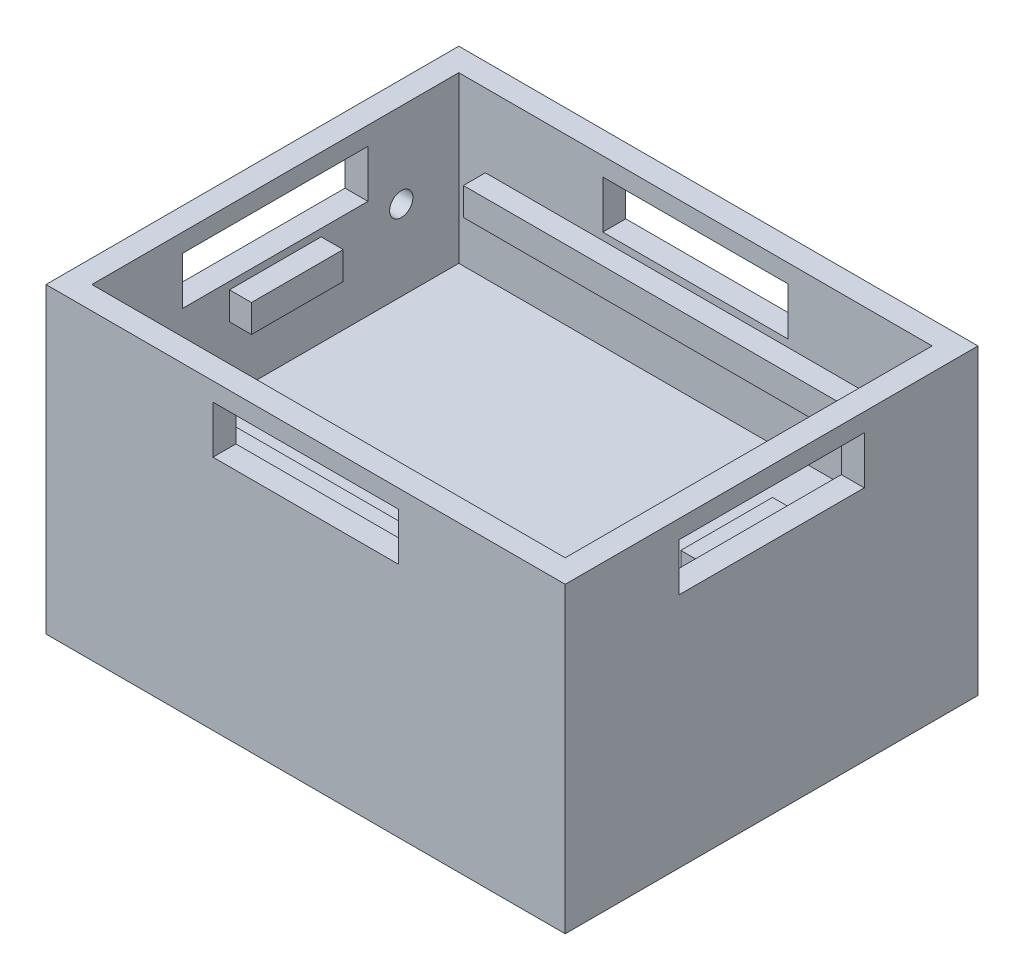
SolidWorks part; units mm, degrees
ref_plane "Front Plane" through (0, 0, 0) normal (0, 0, 1) x (1, 0, 0)
ref_plane "Top Plane" through (0, 0, 0) normal (0, 1, 0) x (1, 0, 0)
ref_plane "Right Plane" through (0, 0, 0) normal (1, 0, 0) x (0, 0, -1)
sketch "Sketch1" plane through (0, 0, 0) normal (0, 1, 0) x (1, 0, 0)
  line L0 (-2.5, 2.5) -> (-2.5, 202.5)
  line L5 (-15, -10) -> (268, -10)
  line L6 (-15, -10) -> (-15, 215)
  line L7 (-15, 215) -> (268, 215)
  line L8 (268, -10) -> (268, 215)
  line L9 (-2.5, 202.5) -> (255.5, 202.5)
  line L10 (255.5, 2.5) -> (255.5, 202.5)
  line L11 (-2.5, 2.5) -> (255.5, 2.5)
  dimension "D1" = 283
  dimension "D2" = 225
  dimension "D3" = 12.5
extrude "Walls" add sketch "Sketch1" along normal blind 90
sketch "Sketch3" plane through (0, 0, 0) normal (0, -1, 0) x (1, 0, 0)
  line L0 (268, -215) -> (-15, -215) construction
  line L1 (268, 10) -> (268, -215) construction
  line L2 (-15, 10) -> (268, 10) construction
  line L3 (-15, -215) -> (-15, 10) construction
  line L4 (268, -215) -> (-15, -215)
  line L5 (268, 10) -> (268, -215)
  line L6 (-15, 10) -> (268, 10)
  line L7 (-15, -215) -> (-15, 10)
extrude "Base" add sketch "Sketch3" along normal blind 12.5
ref_plane "Long_Support_Midplane" through (126.5, 0, 0) normal (1, 0, 0) x (0, 0, -1)
sketch "Sketch4" plane through (126.5, 0, 0) normal (1, 0, 0) x (0, 0, -1)
  line L0 (2.5, 0) -> (2.5, 90)
  line L1 (2.5, 50) -> (14.5, 50)
  line L2 (2.5, 50) -> (2.5, 34.9)
  line L3 (2.5, 34.9) -> (14.5, 34.9)
  line L4 (14.5, 50) -> (14.5, 34.9)
  line L5 (2.5, 0) -> (2.5, 90) construction
  line L6 (202.5, 50) -> (190.5, 50)
  line L7 (202.5, 50) -> (202.5, 34.9)
  line L8 (202.5, 34.9) -> (190.5, 34.9)
  line L9 (190.5, 50) -> (190.5, 34.9)
  line L14 (2.5, 0) -> (202.5, 0)
  line L15 (202.5, 0) -> (202.5, 90)
  line L16 (202.5, 90) -> (2.5, 90)
  line L17 (2.5, 90) -> (2.5, 0)
  line L18 (2.5, 0) -> (202.5, 0) construction
  line L19 (202.5, 0) -> (202.5, 90) construction
  line L20 (202.5, 90) -> (2.5, 90) construction
  line L21 (2.5, 90) -> (2.5, 0) construction
  dimension "D1" = 15.1
  dimension "D2" = 12
  dimension "D4" = 50
extrude "Long_Support" add sketch "Sketch4" along normal mid plane 229
ref_plane "Short_Support_Midplane" through (0, 0, -102.5) normal (0, 0, -1) x (-1, 0, 0)
sketch "Sketch5" plane through (0, 0, -102.5) normal (0, 0, -1) x (-1, 0, 0)
  line L1 (-255.5, 50) -> (-243.5, 50)
  line L2 (-255.5, 50) -> (-255.5, 34.9)
  line L3 (-255.5, 34.9) -> (-243.5, 34.9)
  line L4 (-243.5, 50) -> (-243.5, 34.9)
  line L5 (2.5, 50) -> (-9.5, 50)
  line L6 (2.5, 50) -> (2.5, 34.9)
  line L7 (2.5, 34.9) -> (-9.5, 34.9)
  line L8 (-9.5, 50) -> (-9.5, 34.9)
  line L12 (-255.5, 0) -> (2.5, 0)
  line L13 (2.5, 0) -> (2.5, 90)
  line L14 (2.5, 90) -> (-255.5, 90)
  line L15 (2.5, 0) -> (2.5, 90) construction
  line L16 (-255.5, 0) -> (2.5, 0) construction
  line L20 (-255.5, 90) -> (-255.5, 0)
  line L21 (-255.5, 90) -> (-255.5, 0) construction
  line L22 (2.5, 90) -> (-255.5, 90) construction
  dimension "D4" = 50
  dimension "D2" = 15.1
extrude "Short_Support" add sketch "Sketch5" along normal mid plane 50
sketch "Sketch6" plane through (-2.5, 0, 0) normal (1, 0, 0) x (0, 0, -1)
  line L4 (2.5, 0) -> (202.5, 0)
  line L5 (202.5, 0) -> (202.5, 90)
  line L6 (202.5, 90) -> (2.5, 90)
  line L7 (2.5, 90) -> (2.5, 0)
  line L8 (2.5, 0) -> (202.5, 0) construction
  line L9 (202.5, 0) -> (202.5, 90) construction
  line L10 (202.5, 90) -> (2.5, 90) construction
  line L11 (2.5, 90) -> (2.5, 0) construction
  circle A0 centre (171.15, 43.65) radius 6.35
  dimension "D2" = 12.7
  dimension "D3" = 31.35
  dimension "D4" = 43.65
extrude "Reservoir_Outflow_Tube_Hole" cut sketch "Sketch6" against normal up to next
sketch "Sketch7" plane through (-2.5, 0, 0) normal (1, 0, 0) x (0, 0, -1)
  line L0 (127.5, 50) -> (77.5, 50) construction
  line L1 (52, 54) -> (153, 54)
  line L2 (52, 54) -> (52, 80)
  line L3 (52, 80) -> (153, 80)
  line L4 (153, 54) -> (153, 80)
  line L5 (202.5, 90) -> (2.5, 90) construction
  line L7 (102.5, 80) -> (102.5, 54) construction
  line L8 (102.5, -27.5) -> (102.5, 27.5) construction
  dimension "D1" = 4
  dimension "D2" = 10
  dimension "D3" = 26
  dimension "D4" = 101
extrude "Connector_Port_ShortSide" cut sketch "Sketch7" against normal up to surface (12.5 mm away) up to face at (-15, 43.65, -177.5)
pattern_linear "LPattern1" count 2 spacing 270.5 along (1, 0, 0) of "Connector_Port_ShortSide"
sketch "Sketch8" plane through (0, 0, -2.5) normal (0, 0, 1) x (1, 0, 0)
  line L1 (76, 54) -> (177, 54)
  line L2 (76, 54) -> (76, 80)
  line L3 (76, 80) -> (177, 80)
  line L4 (177, 54) -> (177, 80)
  line L6 (241, 50) -> (12, 50) construction
  line L7 (126.5, 80) -> (126.5, 54) construction
  line L9 (-2.5, 90) -> (255.5, 90) construction
  line L10 (126.5, -28.05) -> (126.5, 28.05) construction
  dimension "D3" = 26
  dimension "D4" = 101
  dimension "D1" = 4
  dimension "D2" = 10
extrude "Connector_Port_LongSide" cut sketch "Sketch8" along normal up to surface (12.5 mm away) contours L4 L3 L2 L1 up to face at (126.5, 38.75, 10)
pattern_linear "LPattern2" count 2 spacing 212.5 along (0, 0, -1) of "Connector_Port_LongSide"
sketch "Sketch9" plane through (0, -12.5, 0) normal (0, -1, 0) x (1, 0, 0)
  line L10 (268, -215) -> (268, 10) construction
  line L11 (-15, -215) -> (268, -215) construction
  line L12 (268, 10) -> (-15, 10) construction
  line L13 (-15, 10) -> (-15, -215) construction
  line L14 (-2.5, -202.5) -> (255.5, -202.5)
  line L15 (255.5, -202.5) -> (255.5, -2.5)
  line L16 (255.5, -2.5) -> (-2.5, -2.5)
  line L17 (-2.5, -2.5) -> (-2.5, -202.5)
  line L18 (-2.5, -202.5) -> (255.5, -202.5)
  line L19 (255.5, -202.5) -> (255.5, -2.5)
  line L20 (255.5, -2.5) -> (-2.5, -2.5)
  line L21 (-2.5, -2.5) -> (-2.5, -202.5)
  line L22 (268, -215) -> (268, 10)
  line L23 (-15, -215) -> (268, -215)
  line L24 (268, 10) -> (-15, 10)
  line L25 (-15, 10) -> (-15, -215)
  dimension "D1" = 12.5
extrude "Lower_Water_Jacket_Walls" add sketch "Sketch9" along normal blind 50
sketch "Sketch11" plane through (0, -62.5, 0) normal (0, -1, 0) x (1, 0, 0)
  line L0 (-15, -215) -> (268, -215) construction
  line L1 (268, -215) -> (268, 10) construction
  line L2 (268, 10) -> (-15, 10) construction
  line L3 (-15, 10) -> (-15, -215) construction
  line L4 (-15, -215) -> (268, -215)
  line L5 (268, -215) -> (268, 10)
  line L6 (268, 10) -> (-15, 10)
  line L7 (-15, 10) -> (-15, -215)
extrude "Lower_Water_Jacket_Bottom" add sketch "Sketch11" along normal blind 12.5
equation "\"Length\" = 283mm"
equation "\"Width\" = 225mm"
equation "\"WallThickness\" = 12.5mm"
equation "\"UpperWaterJacketThickness\" = 28mm"
equation "\"SpacerHeight\" = 80.2mm"
equation "\"PlateLength\" = 252mm"
equation "\"PlateWidth\" = 190mm"
equation "\"PlateHoleDiameter\" = 5.9mm"
equation "\"PlateHoleBottom\" = 2mm"
equation "\"PlateHoleSide\" = 1.55mm"
equation "\"PlateHoleSpacing\" = 3.1mm"
equation "\"PlateThickness\" = 1.55mm"
equation "\"D1@Sketch1\"=\"Length\""
equation "\"D2@Sketch1\"=\"Width\""
equation "\"D3@Sketch1\"=\"WallThickness\""
equation "\"ReservoirBottom\" = 12.5mm"
equation "\"D1@Base\"=\"ReservoirBottom\""
equation "\"ReservoirSupportWidth\" = 12mm"
equation "\"D2@Sketch4\"=\"ReservoirSupportWidth\""
equation "\"ReservoirSupportHeight\" = 15.1mm"
equation "\"D1@Sketch4\"=\"ReservoirSupportHeight\""
equation "\"D1@Sketch5\"=\"ReservoirSupportWidth\""
equation "\"D2@Sketch5\"=\"ReservoirSupportHeight\""
equation "\"ReservoirSupportPlacementHeight\" = 50mm"
equation "\"D4@Sketch5\"=\"ReservoirSupportPlacementHeight\""
equation "\"D4@Sketch4\"=\"ReservoirSupportPlacementHeight\""
equation "\"ReservoirHoleDiameter\" = 12.7mm"
equation "\"D2@Sketch6\"=\"ReservoirHoleDiameter\""
equation "\"ReservoirHoleRight\" = 25mm"
equation "\"D3@Sketch6\"=\"ReservoirHoleRight\"+\"ReservoirHoleDiameter\"/2"
equation "\"ReservoirHoleTop\"= \"ReservoirSupportPlacementHeight\""
equation "\"D4@Sketch6\"=\"ReservoirHoleTop\"-\"ReservoirHoleDiameter\"/2"
equation "\"ReservoirHeight\" = 90mm"
equation "\"D1@Walls\"=\"ReservoirHeight\""
equation "\"ReservoirPortBottom\" = 4mm"
equation "\"D1@Sketch7\"=\"ReservoirPortBottom\""
equation "\"ReservoirPortTop\" = 10mm"
equation "\"D2@Sketch7\"=\"ReservoirPortTop\""
equation "\"ReservoirPortWidth\" = 101mm"
equation "\"D4@Sketch7\"=\"ReservoirPortWidth\""
equation "\"D4@Sketch8\"=\"ReservoirPortWidth\""
equation "\"D1@Sketch8\"=\"ReservoirPortBottom\""
equation "\"D2@Sketch8\"=\"ReservoirPortTop\""
equation "\"D1@Sketch9\"=\"WallThickness\""
equation "\"LowerWaterJacketHeight\"= 50"
equation "\"D1@Lower_Water_Jacket_Walls\" = \"LowerWaterJacketHeight\""
equation "\"LowerWaterJacketBottomThickness\"= \"WallThickness\""
equation "\"D1@Lower_Water_Jacket_Bottom\" = \"LowerWaterJacketBottomThickness\""
